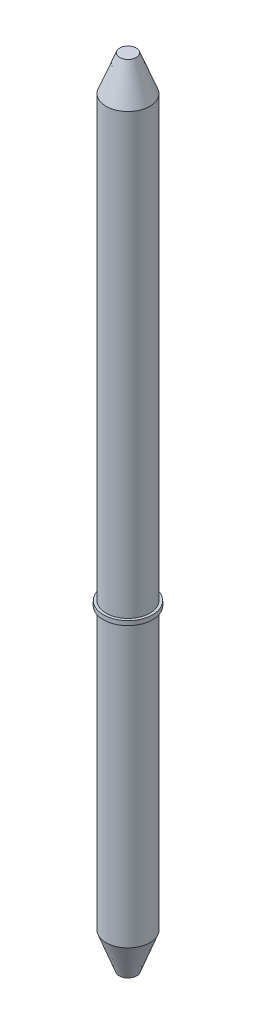
SolidWorks part; units mm, degrees
material "2014 Alloy"
ref_plane "Front Plane" through (0, 0, 0) normal (0, 0, 1) x (1, 0, 0)
ref_plane "Top Plane" through (0, 0, 0) normal (0, 1, 0) x (1, 0, 0)
ref_plane "Right Plane" through (0, 0, 0) normal (1, 0, 0) x (0, 0, -1)
sketch "Sketch1" plane through (0, 0, 0) normal (0, 1, 0) x (1, 0, 0)
  circle A0 centre (0, 0) radius 63.5
extrude "Boss-Extrude1" add sketch "Sketch1" along normal blind 812.8
sketch "Sketch2" plane through (0, 812.8, 0) normal (0, 1, 0) x (1, 0, 0)
  circle A0 centre (0, 0) radius 71.1286
extrude "Boss-Extrude2" add sketch "Sketch2" along normal blind 12.7
sketch "Sketch3" plane through (0, 825.5, 0) normal (0, 1, 0) x (1, 0, 0)
  circle A0 centre (0, 0) radius 63.5
extrude "Boss-Extrude3" add sketch "Sketch3" along normal blind 1270
sketch "Sketch4" plane through (0, 0, 0) normal (1, 0, 0) x (0, 0, -1)
  line L0 (63.5, 2095.5) -> (0, 2095.5)
  line L1 (63.5, 2095.5) -> (-63.5, 2095.5) construction
  line L2 (0, 2095.5) -> (0, 2197.892)
  line L3 (0, 2197.892) -> (23.8701, 2197.892)
  line L4 (23.8701, 2197.892) -> (63.5, 2095.5)
revolve "Revolve1" add sketch "Sketch4" angle 360 about L2
sketch "Sketch5" plane through (0, 0, 0) normal (1, 0, 0) x (0, 0, -1)
  line L0 (-63.5, 0) -> (0, 0)
  line L1 (-63.5, 0) -> (63.5, 0) construction
  line L2 (0, 0) -> (0, -102.2194)
  line L3 (0, -102.2194) -> (-25.4482, -102.2194)
  line L4 (-25.4482, -102.2194) -> (-63.5, 0)
revolve "Revolve2" add sketch "Sketch5" angle 360 about L2
